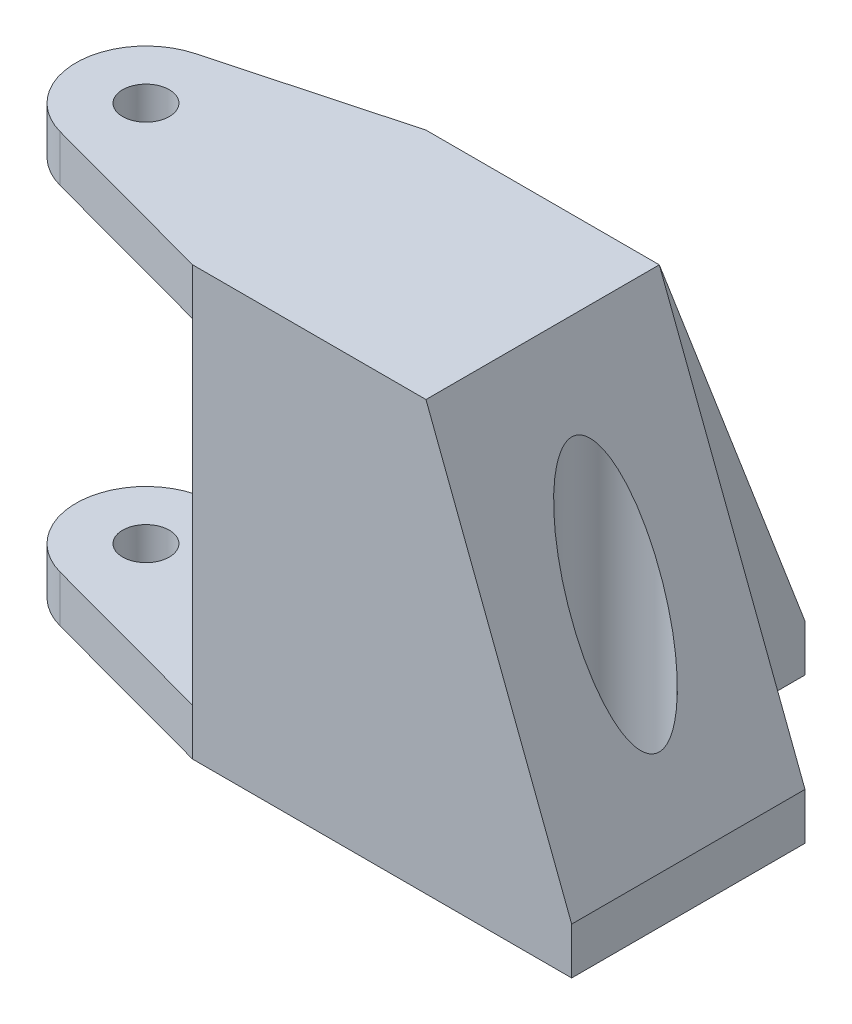
SolidWorks part; units mm, degrees
ref_plane "Front Plane" through (0, 0, 0) normal (0, 0, 1) x (1, 0, 0)
ref_plane "Top Plane" through (0, 0, 0) normal (0, 1, 0) x (1, 0, 0)
ref_plane "Right Plane" through (0, 0, 0) normal (1, 0, 0) x (0, 0, -1)
sketch "Sketch2" plane through (0, 0, 0) normal (0, 0, 1) x (1, 0, 0)
  line L0 (0, 0) -> (-40, 0)
  line L1 (0, 73.3918) -> (24.9782, 8)
  line L2 (24.9782, 8) -> (24.9782, 0)
  line L3 (0, 0) -> (24.9782, 0)
  line L4 (-40, 0) -> (-40, 73.3918)
  line L5 (-40, 73.3918) -> (0, 73.3918)
  dimension "D1" = 40
  dimension "D2" = 8
  dimension "D3" = 70
extrude "Boss-Extrude1" add sketch "Sketch2" along normal blind 40
sketch "Sketch3" plane through (0, 73.3918, 0) normal (0, 1, 0) x (1, 0, 0)
  line L0 (-40, -40) -> (-40, 0) construction
  line L1 (-40, -40) -> (-71.1316, -31.5842)
  line L2 (-40, 0) -> (-71.1316, -8.4158)
  line L3 (-40, 0) -> (-40, -40)
  arc A0 (-71.1316, -31.5842) -> (-71.1316, -8.4158) centre (-68, -20) cw
  point P3 (-80, -20)
  dimension "D2" = 20
  dimension "D1" = 40
extrude "Boss-Extrude2" add sketch "Sketch3" against normal up to vertex (73.3918 mm away) contours L1 A0 L2 L3 up to point (-40, 0, 40)
sketch "Sketch4" plane through (0, 0, 0) normal (0, 0, 1) x (1, 0, 0)
  line L0 (-40, 73.3918) -> (-40, 65.3918) construction
  line L1 (-40, 73.3918) -> (-40, 0) construction
  line L2 (-40, 73.3918) -> (-71.1316, 73.3918) construction
  line L3 (-40, 0) -> (-40, 8) construction
  line L4 (22, 0) -> (-22, 0) construction
  line L5 (-40, 8) -> (-40, 65.3918)
  line L6 (-40, 65.3918) -> (-80, 65.3918)
  line L7 (-80, 73.3918) -> (-80, 0) construction
  line L8 (-80, 65.3918) -> (-80, 8)
  line L9 (-80, 8) -> (-40, 8)
  dimension "D1" = 8
  dimension "D2" = 8
extrude "Cut-Extrude1" cut sketch "Sketch4" along normal blind 73
sketch "Sketch5" plane through (0, 0, 0) normal (1, 0, 0) x (0, 0, -1)
  line L0 (0, 0) -> (24.9782, 0)
  line L1 (22, 0) -> (-22, 0) construction
  line L2 (24.9782, 0) -> (24.9782, 8)
  line L3 (24.9782, 8) -> (0, 73.3918)
  line L4 (0, 40.3655) -> (0, -40.3655) construction
  line L5 (-40, 73.3918) -> (0, 73.3918) construction
  line L6 (0, 73.3918) -> (0, 0)
  dimension "D1" = 70
  dimension "D2" = 8
extrude "Boss-Extrude3" add sketch "Sketch5" against normal blind 40
sketch "Sketch6" plane through (0, 73.3918, 0) normal (0, 1, 0) x (1, 0, 0)
  circle A0 centre (-68, -20) radius 4
  circle A1 centre (-20, 12.4891) radius 4
  circle A2 centre (12.4891, -20) radius 4
  dimension "D1" = 8
  dimension "D2" = 8
  dimension "D3" = 8
extrude "Cut-Extrude2" cut sketch "Sketch6" against normal through all
ref_plane "Plane1" through (0, 5, 0) normal (0, 1, 0) x (1, 0, 0)
sketch "Sketch8" plane through (0, 5, 0) normal (0, 1, 0) x (1, 0, 0)
  circle A0 centre (-20, 12.4891) radius 7.5
  circle A1 centre (12.4891, -20) radius 7.5
  dimension "D1" = 15
  dimension "D2" = 15
extrude "Cut-Extrude3" cut sketch "Sketch8" along normal through all
